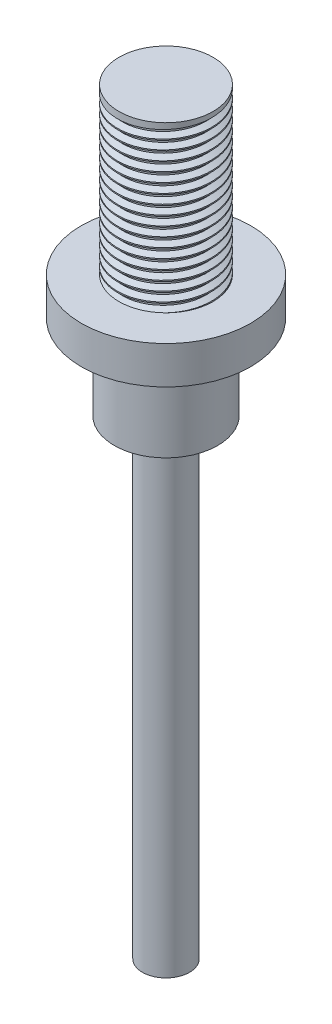
SolidWorks part; units mm, degrees
ref_plane "Front" through (0, 0, 0) normal (0, 0, 1) x (1, 0, 0)
ref_plane "Top" through (0, 0, 0) normal (0, 1, 0) x (1, 0, 0)
ref_plane "Right" through (0, 0, 0) normal (1, 0, 0) x (0, 0, -1)
sketch "Sketch1" plane through (0, 0, 0) normal (0, 1, 0) x (1, 0, 0)
  circle A0 centre (0, 0) radius 9
  dimension "D1" = 18
extrude "Boss-Extrude1" add sketch "Sketch1" along normal blind 4
sketch "Sketch2" plane through (0, 4, 0) normal (0, 1, 0) x (1, 0, 0)
  circle A0 centre (0, 0) radius 5
  dimension "D1" = 10
extrude "Boss-Extrude2" add sketch "Sketch2" along normal blind 17.5
sketch "Sketch3" plane through (0, 0, 0) normal (0, -1, 0) x (1, 0, 0)
  circle A0 centre (0, 0) radius 5.5
  dimension "D1" = 11
extrude "Boss-Extrude3" add sketch "Sketch3" along normal blind 9
thread "Thread1" pitch 1 method cut profile "Thread Profile1" start angle 0, offset 0, length 0, pitch 1, diameter 10
ref_plane "Plane1" through (-5, 21.5, 0) normal (0, 0, 1) x (-1, 0, 0)
sketch "Thread Profile1" plane through (-5, 21.5, 0) normal (0, 0, 1) x (-1, 0, 0)
  line L0 (0, 0) -> (0, 1) construction
  line L11 (0, 0) -> (0, 0.875)
  line L12 (0, 0.875) -> (-0.5413, 0.5625)
  line L13 (-0.5413, 0.5625) -> (-0.5413, 0.3125)
  line L15 (-0.5413, 0.3125) -> (0, 0)
  line L17 (-0.5413, 0.4375) -> (0, 0.4375) construction
  point P2 (0, 0)
  dimension "Pitch" = 1
  dimension "Profile_Angle" = 60
  dimension "Profile_Land" = 0.25
  dimension "Profile_Height" = 0.5413
sketch "Sketch6" plane through (0, -9, 0) normal (0, -1, 0) x (1, 0, 0)
  circle A0 centre (0, 0) radius 2.5
  dimension "D1" = 5
extrude "Boss-Extrude4" add sketch "Sketch6" along normal blind 50
